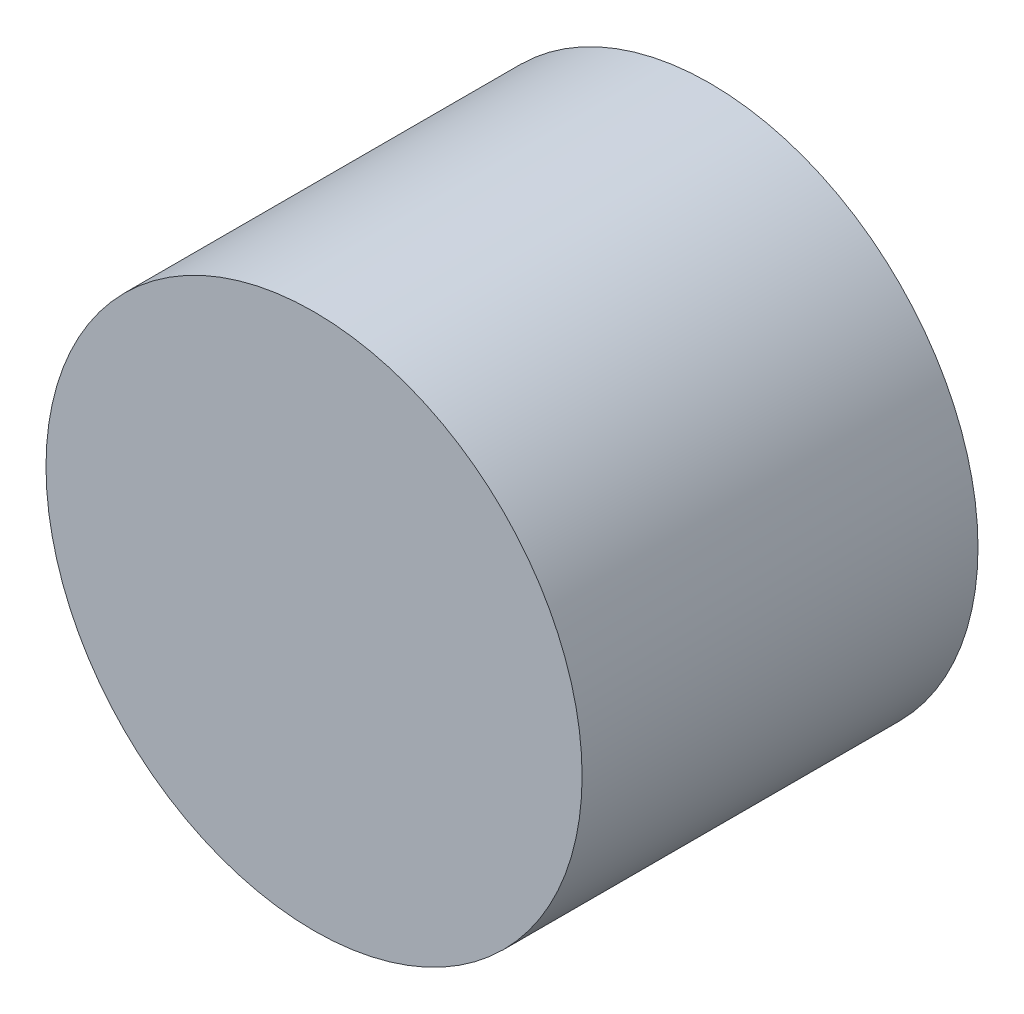
SolidWorks part; units mm, degrees
ref_plane "Front Plane" through (0, 0, 0) normal (0, 0, 1) x (1, 0, 0)
ref_plane "Top Plane" through (0, 0, 0) normal (0, 1, 0) x (1, 0, 0)
ref_plane "Right Plane" through (0, 0, 0) normal (1, 0, 0) x (0, 0, -1)
sketch "Sketch1" plane through (0, 0, 0) normal (0, 0, 1) x (1, 0, 0)
  circle A0 centre (0, 0) radius 103.1875
  dimension "D1" = 206.375
extrude "Boss-Extrude1" add sketch "Sketch1" along normal blind 152.4
sketch "Sketch2" plane through (0, 0, 0) normal (0, 0, -1) x (-1, 0, 0)
  circle A0 centre (0, 0) radius 101.6
  circle A1 centre (0, 0) radius 103.1875 construction
  dimension "D1" = 1.5875
extrude "Cut-Extrude1" cut sketch "Sketch2" against normal blind 149.225
sketch "Sketch3" plane through (0, 0, 0) normal (1, 0, 0) x (0, 0, -1)
  line L0 (-149.225, 0) -> (0, 0) construction
  line L1 (-149.225, -101.6) -> (-149.225, 101.6) construction
  line L2 (0, -103.1875) -> (0, 103.1875) construction
  line L3 (0, -101.6) -> (0, 101.6) construction
  circle A0 centre (-142.875, 0) radius 6.35
  dimension "D1" = 12.7
extrude "Cut-Extrude2" cut sketch "Sketch3" against normal through all
